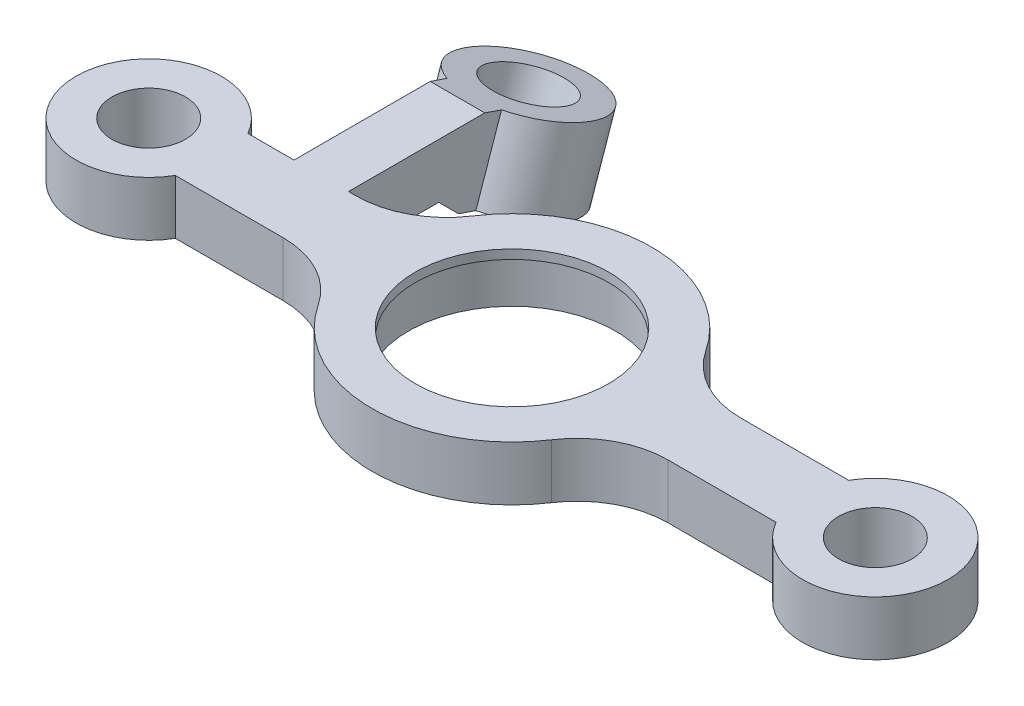
SolidWorks part; units mm, degrees
material "ABS"
ref_plane "Plano frontal" through (0, 0, 0) normal (0, 0, 1) x (1, 0, 0)
ref_plane "Plano superior" through (0, 0, 0) normal (0, 1, 0) x (1, 0, 0)
ref_plane "Plano direito" through (0, 0, 0) normal (1, 0, 0) x (0, 0, -1)
sketch "Esboço1" plane through (0, 0, 0) normal (0, 1, 0) x (1, 0, 0)
  line L0 (-40, 0) -> (40, 0) construction
  line L1 (-33.0718, 4) -> (-28, 4)
  line L2 (-33.0718, -4) -> (-21.1934, -4)
  line L3 (21.1934, 4) -> (33.0718, 4)
  line L4 (21.1934, -4) -> (33.0718, -4)
  line L5 (-28, 4) -> (-28, 19)
  line L6 (-22, 4) -> (-21.1934, 4)
  line L7 (-22, 19) -> (-22, 4)
  line L8 (-25, 25.1417) -> (-25, 0) construction
  line L9 (-28, 19) -> (-22, 19)
  arc A0 (-33.0718, 4) -> (-33.0718, -4) centre (-40, 0) ccw
  arc A1 (33.0718, -4) -> (33.0718, 4) centre (40, 0) ccw
  circle A2 centre (40, 0) radius 4.05
  circle A3 centre (-40, 0) radius 4.05
  arc A4 (-12.8495, -8.4882) -> (12.8495, -8.4882) centre (0, 0) ccw
  arc A5 (12.8495, 8.4882) -> (-12.8495, 8.4882) centre (0, 0) ccw
  circle A6 centre (0, 0) radius 11.4
  arc A7 (-12.8495, -8.4882) -> (-21.1934, -4) centre (-21.1934, -14) ccw
  arc A8 (21.1934, -4) -> (12.8495, -8.4882) centre (21.1934, -14) ccw
  arc A9 (21.1934, 4) -> (12.8495, 8.4882) centre (21.1934, 14) cw
  arc A10 (-12.8495, 8.4882) -> (-21.1934, 4) centre (-21.1934, 14) cw
  point P4 (0, 0)
  point P22 (14.8714, 4)
  dimension "D2" = 8.1
  dimension "D3" = 16
  dimension "D5" = 4
  dimension "D6" = 22.8
  dimension "D7" = 10
  dimension "D10" = 15
  dimension "D1" = 80
  dimension "D4" = 8
  dimension "D8" = 25
  dimension "D9" = 6
extrude "Ressalto-extrusão1" add sketch "Esboço1" along normal blind 6
sketch "Esboço2" plane through (0, 6, 0) normal (0, 1, 0) x (1, 0, 0)
  circle A0 centre (0, 0) radius 10.65
  circle A1 centre (0, 0) radius 11.4
  circle A2 centre (0, 0) radius 11.4 construction
  dimension "D1" = 0.75
extrude "Ressalto-extrusão2" add sketch "Esboço2" against normal blind 1
sketch "Esboço3" plane through (-28, 0, 0) normal (-1, 0, 0) x (0, 0, 1)
  line L0 (-19, 0) -> (-15.0073, -11.5957) construction
  line L1 (-19, 0) -> (-4, 0) construction
  dimension "D1" = 71
ref_plane "Plano1" through (0, 5.8488, -2.0139) normal (0, -0.9455, 0.3256) x (-1, 0, 0)
sketch "Esboço4" plane through (0, 5.8488, -2.0139) normal (0, -0.9455, 0.3256) x (-1, 0, 0)
  line L0 (22, 17.9649) -> (28, 17.9649) construction
  line L1 (28, 16.0114) -> (22, 16.0114)
  line L2 (22, 3.7821) -> (22, 17.9649) construction
  line L3 (22, 16.0114) -> (22, 17.9649)
  line L4 (28, 17.9649) -> (28, 16.0114)
  arc A0 (28, 17.9649) -> (22, 17.9649) centre (25, 24.2894) ccw
  circle A1 centre (25, 24.2894) radius 4.15
  point P7 (25, 17.9649)
  point P15 (28, 16.0114)
  dimension "D1" = 14
  dimension "D2" = 8.3
extrude "Ressalto-extrusão4" add sketch "Esboço4" against normal up to vertex (5.6731 mm away) and the other way blind 3 up to point (-22, 6, -19)
chamfer "Chanfro1" distance 3 angle 45 1 edges at (-25, 0, -16.934) first distance on face at (0, 0, 11.4)
